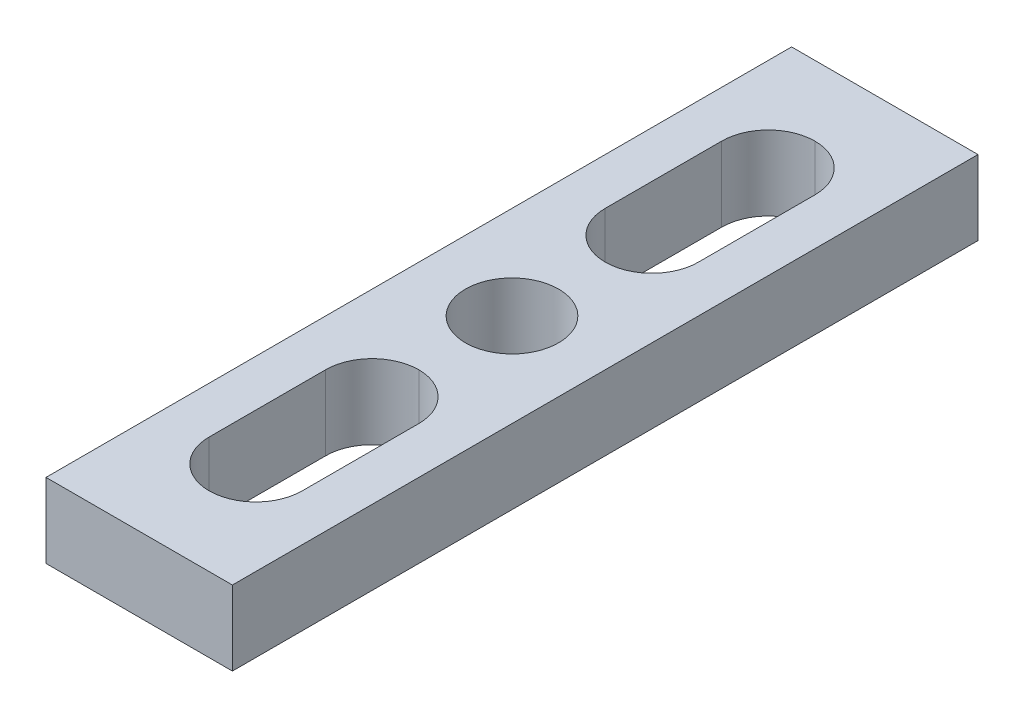
SolidWorks part; units mm, degrees
material "1060 Alloy"
ref_plane "Front Plane" through (0, 0, 0) normal (0, 0, 1) x (1, 0, 0)
ref_plane "Top Plane" through (0, 0, 0) normal (0, 1, 0) x (1, 0, 0)
ref_plane "Right Plane" through (0, 0, 0) normal (1, 0, 0) x (0, 0, -1)
sketch "Sketch1" plane through (0, 0, 0) normal (0, 0, 1) x (1, 0, 0)
  line L0 (55, 0) -> (-55, 0) construction
  line L1 (-12.7, 10.16) -> (12.7, 10.16)
  line L2 (-12.7, 10.16) -> (-12.7, 0)
  line L3 (-12.7, 0) -> (12.7, 0)
  line L4 (12.7, 10.16) -> (12.7, 0)
  line L5 (0, -55) -> (0, 55) construction
  dimension "D1" = 10.16
  dimension "D2" = 25.4
  dimension "D3" = 12.7
extrude "Boss-Extrude1" add sketch "Sketch1" along normal blind 101.6
sketch "Sketch2" plane through (0, 10.16, 0) normal (0, 1, 0) x (1, 0, 0)
  line L0 (0, -55) -> (0, 55) construction
  line L1 (-55, 0) -> (55, 0) construction
  circle A0 centre (0, -50.8) radius 6.35
  dimension "D1" = 50.8
extrude "Cut-Extrude1" cut sketch "Sketch2" against normal blind 88.9
sketch "Sketch3" plane through (0, 10.16, 0) normal (0, 1, 0) x (1, 0, 0)
  line L0 (-5.588, 0) -> (5.588, 0) construction
  line L1 (-6.35, -9.525) -> (6.35, -9.525)
  line L2 (-6.35, -9.525) -> (-6.35, -38.1)
  line L3 (-6.35, -38.1) -> (6.35, -38.1)
  line L4 (6.35, -9.525) -> (6.35, -38.1)
  line L5 (-6.35, -92.075) -> (6.35, -92.075)
  line L6 (-6.35, -92.075) -> (-6.35, -63.5)
  line L7 (-6.35, -63.5) -> (6.35, -63.5)
  line L8 (6.35, -92.075) -> (6.35, -63.5)
  line L9 (12.7, -101.6) -> (-12.7, -101.6) construction
  line L10 (12.7, -101.6) -> (12.7, 0) construction
  dimension "D1" = 12.7
  dimension "D2" = 9.525
  dimension "D3" = 28.575
  dimension "D4" = 9.525
  dimension "D5" = 6.35
extrude "Cut-Extrude2" cut sketch "Sketch3" against normal blind 12.7
fillet "Fillet1" radius 6.35 8 edges at (6.35, 5.08, 38.1) (6.35, 5.08, 92.075) (-6.35, 5.08, 92.075) (-6.35, 5.08, 38.1) (6.35, 5.08, 63.5) (6.35, 5.08, 9.525) (-6.35, 5.08, 9.525) (-6.35, 5.08, 63.5)
